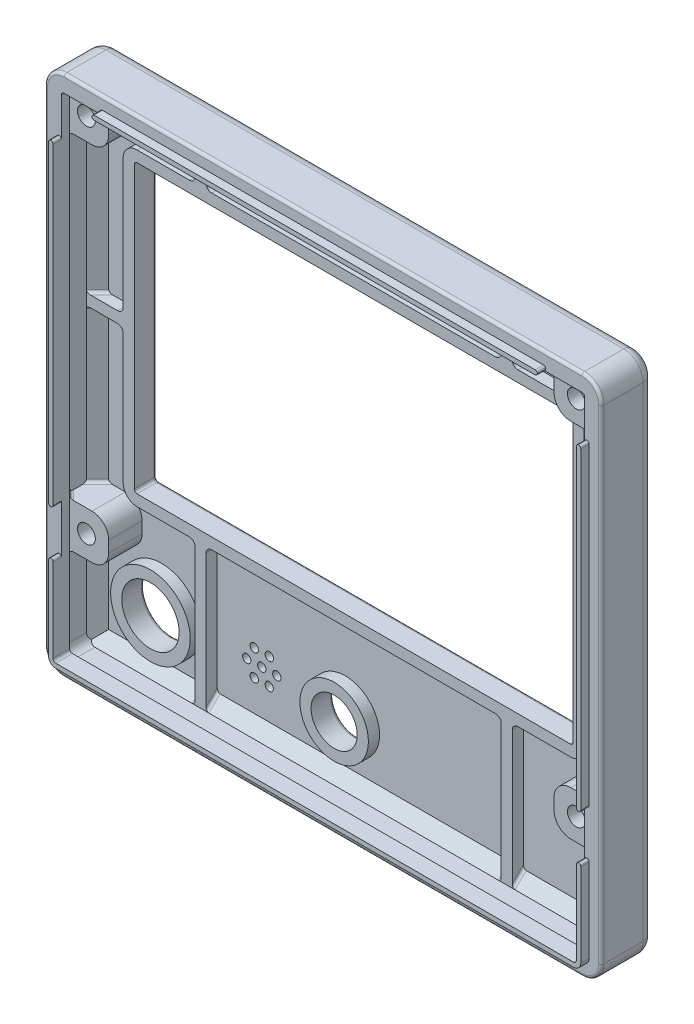
SolidWorks part; units mm, degrees
ref_plane "Спереди" through (0, 0, 0) normal (0, 0, 1) x (1, 0, 0)
ref_plane "Сверху" through (0, 0, 0) normal (0, 1, 0) x (1, 0, 0)
ref_plane "Справа" through (0, 0, 0) normal (1, 0, 0) x (0, 0, -1)
sketch "Эскиз1" plane through (0, 0, 0) normal (0, 0, 1) x (1, 0, 0)
  line L1 (-50, 46.95) -> (50, 46.95)
  line L2 (-50, 46.95) -> (-50, -46.95)
  line L3 (-50, -46.95) -> (50, -46.95)
  line L4 (50, 46.95) -> (50, -46.95)
  line L5 (-50, 46.95) -> (50, -46.95) construction
  line L6 (-50, -46.95) -> (50, 46.95) construction
  point P0 (0, 0)
  dimension "D1" = 100
  dimension "D2" = 93.9
extrude "Бобышка-Вытянуть1" add sketch "Эскиз1" along normal blind 2
sketch "Эскиз2" plane through (0, 0, 2) normal (0, 0, 1) x (1, 0, 0)
  line L0 (-48, -44.95) -> (48, -44.95)
  line L1 (50, -46.95) -> (-50, -46.95)
  line L2 (50, -46.95) -> (50, 46.95)
  line L3 (50, 46.95) -> (-50, 46.95)
  line L4 (-50, -46.95) -> (-50, 46.95)
  line L5 (50, -46.95) -> (-50, 46.95) construction
  line L6 (50, 46.95) -> (-50, -46.95) construction
  line L7 (48, -44.95) -> (48, -28.05)
  line L8 (48, -28.05) -> (40, -28.05)
  line L9 (40, -28.05) -> (40, -20.05)
  line L10 (40, -20.05) -> (48, -20.05)
  line L11 (48, -20.05) -> (48, 36.95)
  line L12 (48, 36.95) -> (40, 36.95)
  line L13 (40, 36.95) -> (40, 44.95)
  line L14 (40, 44.95) -> (-40, 44.95)
  line L15 (-40, 44.95) -> (-40, 36.95)
  line L16 (-40, 36.95) -> (-48, 36.95)
  line L17 (-48, 36.95) -> (-48, -20.05)
  line L18 (-48, -20.05) -> (-40, -20.05)
  line L19 (-40, -20.05) -> (-40, -28.05)
  line L20 (-40, -28.05) -> (-48, -28.05)
  line L21 (-48, -28.05) -> (-48, -44.95)
  line L22 (0, -3.7934) -> (0, 11.2679) construction
  line L23 (-44, 40.95) -> (44, 40.95) construction
  line L24 (-50, 46.95) -> (-28.7577, 25.7077) construction
  line L25 (44, -24.05) -> (-44, -24.05) construction
  line L26 (-44, -24.05) -> (-31.995, -12.045) construction
  line L27 (-41.4, 36.2) -> (41.4, 36.2)
  line L28 (-39.4, 34.2) -> (39.4, 34.2)
  line L29 (-39.4, 34.2) -> (-39.4, -17.3)
  line L30 (-39.4, -17.3) -> (39.4, -17.3)
  line L31 (39.4, 34.2) -> (39.4, -17.3)
  line L32 (-39.4, 34.2) -> (39.4, -17.3) construction
  line L33 (-39.4, -17.3) -> (39.4, 34.2) construction
  line L34 (41.4, 36.2) -> (41.4, -19.3)
  line L35 (-41.4, -19.3) -> (41.4, -19.3)
  line L36 (-41.4, 36.2) -> (-41.4, -19.3)
  line L37 (-45.7536, -35.05) -> (46.2117, -35.05) construction
  circle A0 centre (-44, 40.95) radius 1.6
  circle A1 centre (44, 40.95) radius 1.6
  circle A2 centre (-44, -24.05) radius 1.6
  circle A3 centre (44, -24.05) radius 1.6
  circle A4 centre (-36.5, -35.05) radius 5.15
  circle A5 centre (-18.5, -35.05) radius 0.75
  circle A6 centre (-21.2, -35.05) radius 0.75
  circle A7 centre (-3.5, -35.05) radius 4.15
  circle A8 centre (-19.85, -32.7117) radius 0.75
  circle A9 centre (-17.15, -32.7117) radius 0.75
  circle A10 centre (-15.8, -35.05) radius 0.75
  circle A11 centre (-17.15, -37.3883) radius 0.75
  circle A12 centre (-19.85, -37.3883) radius 0.75
  circle A13 centre (-3.5, -35.05) radius 6.15
  circle A14 centre (-36.5, -35.05) radius 7.15
  point P0 (0, 0)
  point P7 (0, 0)
  point P19 (0, 44.95)
  point P30 (0, 40.95)
  point P37 (40, -24.05)
  point P39 (0, 8.45)
  point P40 (0, -24.05)
  point P71 (-18.5, -35.05)
  line M5 (50, -46.95) -> (50, 46.95)
  line M6 (50, 46.95) -> (-50, 46.95)
  line M7 (-50, 46.95) -> (-50, -46.95)
  line M8 (-50, -46.95) -> (50, -46.95)
  dimension "D6" = 3.2
  dimension "D18" = 10.3
  dimension "D19" = 1.5
  dimension "D22" = 8.3
  dimension "D1" = 2
  dimension "D2" = 2
  dimension "D3" = 2
  dimension "D4" = 88
  dimension "D5" = 45
  dimension "D7" = 65
  dimension "D8" = 45
  dimension "D9" = 10
  dimension "D10" = 51.5
  dimension "D11" = 78.8
  dimension "D12" = 32.5
  dimension "D14" = 11
  dimension "D15" = 15
  dimension "D16" = 18
  dimension "D17" = 7.5
  dimension "D20" = 2.7
  dimension "D13" = 2
  dimension "D23" = 2
  dimension "D21" = 6
extrude "Бобышка-Вытянуть2" add sketch "Эскиз2" along normal blind 6 contours A3 A2 A1 A0 L21 L20 L19 L18 L17 L16 L15 L14 L13 L12 L11 L10 L9 L8 L7 L0 M8 M5 M6 M7 region at (0, -45.5782, 2)
ref_plane "Плоскость1" through (44, 0, 0) normal (1, 0, 0) x (0, 0, -1)
sketch "Эскиз6" plane through (44, 0, 0) normal (1, 0, 0) x (0, 0, -1)
  line L0 (-8, 42.55) -> (-8, 39.35) construction
  line L1 (-11.8886, 40.95) -> (4.8628, 40.95) construction
  line L2 (-8, 40.95) -> (-8, 42.55)
  line L3 (-8, -46.95) -> (-8, 46.95) construction
  line L4 (-8, 42.55) -> (-1.65, 42.55)
  line L5 (-1.65, 42.55) -> (-0.45, 43.75)
  line L6 (-0.45, 43.75) -> (0, 43.75)
  line L7 (0, -46.95) -> (0, 46.95) construction
  line L8 (0, 43.75) -> (0, 40.95)
  line L9 (0, 40.95) -> (-8, 40.95)
  point P2 (-8, 40.95)
  dimension "D1" = 5.6
  dimension "D2" = 1.65
  dimension "D3" = 45
  dimension "D4" = 3.2
revolve "Вырез-Повернуть1" cut sketch "Эскиз6" angle 360 about L1
pattern_linear "Линейный массив1" count 2 spacing 65 along (0, -1, 0) of "Вырез-Повернуть1"
mirror "Зеркальное отражение1" about plane through (0, 0, 0) normal (1, 0, 0) of "Линейный массив1", "Вырез-Повернуть1"
sketch "Эскиз3" plane through (0, 0, 8) normal (0, 0, 1) x (1, 0, 0)
  line L0 (40, 44.95) -> (-40, 44.95) construction
  line L1 (50, -46.95) -> (-50, -46.95)
  line L2 (50, -46.95) -> (50, 46.95)
  line L3 (50, 46.95) -> (-50, 46.95)
  line L4 (-50, -46.95) -> (-50, 46.95)
  line L5 (50, -46.95) -> (-50, 46.95) construction
  line L6 (50, 46.95) -> (-50, -46.95) construction
  line L7 (47, -43.95) -> (-47, -43.95)
  line L8 (47, -43.95) -> (47, 43.95)
  line L9 (47, 43.95) -> (-47, 43.95)
  line L10 (-47, -43.95) -> (-47, 43.95)
  line L11 (47, -43.95) -> (-47, 43.95) construction
  line L12 (47, 43.95) -> (-47, -43.95) construction
  line L13 (-48, -28.05) -> (-48, -44.95) construction
  point P0 (0, 0)
  point P7 (0, 0)
  dimension "D1" = 1
  dimension "D2" = 1
extrude "Бобышка-Вытянуть3" add sketch "Эскиз3" along normal blind 1.5
sketch "Эскиз4" plane through (0, 0, 9.5) normal (0, 0, 1) x (1, 0, 0)
  line L0 (-47, -43.95) -> (-47, -28.05)
  line L1 (-47, -28.05) -> (-47.8, -28.05)
  line L2 (-47.8, -28.05) -> (-47.8, -44.75)
  line L3 (-47.8, -44.75) -> (47.8, -44.75)
  line L4 (47.8, -44.75) -> (47.8, -28.05)
  line L5 (47.8, -28.05) -> (47, -28.05)
  line L6 (47, -28.05) -> (47, -43.95)
  line L7 (47, -43.95) -> (-47, -43.95)
  line L8 (-47, -20.05) -> (-47, 36.95)
  line L9 (-40, 36.95) -> (-48, 36.95) construction
  line L11 (-47, 36.95) -> (-47.8, 36.95)
  line L12 (-47.8, 36.95) -> (-47.8, -20.05)
  line L13 (-47.8, -20.05) -> (-47, -20.05)
  line L14 (47, -20.05) -> (47, 36.95)
  line L15 (47, 36.95) -> (47.8, 36.95)
  line L16 (47.8, 36.95) -> (47.8, -20.05)
  line L17 (47.8, -20.05) -> (47, -20.05)
  line L18 (-40, 43.95) -> (-40, 44.75)
  line L19 (-40, 44.75) -> (40, 44.75)
  line L20 (40, 44.75) -> (40, 43.95)
  line L21 (40, 43.95) -> (-40, 43.95)
  dimension "D1" = 0.8
  dimension "D2" = 0.8
extrude "Бобышка-Вытянуть4" add sketch "Эскиз4" along normal blind 1.5
extrude "Вырез-Вытянуть1" cut sketch "Эскиз2<3>" against normal through all contours L31 L28 L29 L30 | A4 | A6 | A5 | A8 | A9 | A10 | A11 | A12 | A7 region at (0, 8.45, 2) region at (-36.5, -35.05, 2) region at (-18.5, -35.05, 2) region at (-21.2, -35.05, 2) region at (-3.5, -35.05, 2) region at (-19.85, -32.7117, 2) region at (-17.15, -32.7117, 2) region at (-15.8, -35.05, 2) region at (-17.15, -37.3883, 2) region at (-19.85, -37.3883, 2)
sketch "Эскиз2<3>" plane through (0, 0, 2) normal (0, 0, 1) x (1, 0, 0) same geometry as "Эскиз2"
extrude "Бобышка-Вытянуть5" add sketch "Эскиз2<4>" along normal blind 2 contours A14 A4 | A13 A7 | L27 L36 L35 L34 L28 L31 L30 L29 region at (0, 35.2032, 2) region at (-9.4761, -35.05, 2) region at (-43.4478, -35.05, 2)
sketch "Эскиз2<4>" plane through (0, 0, 2) normal (0, 0, 1) x (1, 0, 0) same geometry as "Эскиз2"
fillet "Скругление1" radius 3 6 edges at (40, -20.05, 5) (40, -28.05, 5) (40, 36.95, 5) (-40, -20.05, 5) (-40, -28.05, 5) (-40, 36.95, 5)
fillet "Скругление2" radius 0.5 4 edges at (47, -43.95, 9.5) (47, 43.95, 8.75) (-47, 43.95, 8.75) (-47, -43.95, 9.5)
fillet "Скругление3" radius 1.3 2 edges at (47.8, -44.75, 10.25) (-47.8, -44.75, 10.25)
fillet "Скругление4" radius 3.5 4 edges at (50, 46.95, 4.75) (-50, 46.95, 4.75) (-50, -46.95, 4.75) (50, -46.95, 4.75)
fillet "Скругление5" radius 0.4 16 edges at (-47, 36.95, 10.25) (-47.8, 36.95, 10.25) (-40, 44.75, 10.25) (-40, 43.95, 10.25) (40, 44.75, 10.25) (40, 43.95, 10.25) (47.8, 36.95, 10.25) (47, 36.95, 10.25) (47.8, -20.05, 10.25) (47, -20.05, 10.25) (47.8, -28.05, 10.25) (-47.8, -28.05, 10.25) (-47, -20.05, 10.25) (-47.8, -20.05, 10.25)
fillet "Скругление11" radius 2 8 edges at (-48.9749, -45.9249, 0) (-50, 0, 0) (-48.9749, 45.9249, 0) (0, 46.95, 0) (48.9749, 45.9249, 0) (50, 0, 0) (48.9749, -45.9249, 0) (0, -46.95, 0)
fillet "Скругление12" radius 0.5 8 edges at (-48.9749, 45.9249, 9.5) (0, 46.95, 9.5) (48.9749, 45.9249, 9.5) (50, 0, 9.5) (48.9749, -45.9249, 9.5) (0, -46.95, 9.5) (-48.9749, -45.9249, 9.5) (-50, 0, 9.5)
fillet "Скругление14" radius 0.5 10 edges at (0, 34.2, 0) (-39.4, 8.45, 0) (39.4, 8.45, 0) (0, -17.3, 0) (39.4, -17.3, 2) (39.4, 34.2, 2) (-39.4, 34.2, 2) (-39.4, -17.3, 2) (-31.35, -35.05, 0) (0.65, -35.05, 0)
fillet "Скругление15" radius 2.5 4 edges at (-41.4, -19.3, 3) (-41.4, 36.2, 3) (41.4, 36.2, 3) (41.4, -19.3, 3)
sketch "Эскиз5" plane through (0, 0, 2) normal (0, 0, 1) x (1, 0, 0)
  line L0 (-18.5, -35.05) -> (-36.5, -35.05) construction
  line L1 (0, 17.7413) -> (0, -7.0875) construction
  line L2 (-27.5, -51.2657) -> (-27.5, 49.7619) construction
  line L3 (27.5, -48.9866) -> (-27.5, -48.9866) construction
  line L4 (27.5, -51.2657) -> (27.5, 49.7619) construction
  line L5 (-39.4, 33.7) -> (-39.4, -16.8) construction
  line L6 (-62.052, 8.45) -> (56.1888, 8.45) construction
  line L7 (-38.9, -19.3) -> (38.9, -19.3) construction
  line L8 (-28.5, 44.95) -> (-26.5, 44.95)
  line L9 (-28.5, 44.95) -> (-28.5, 36.2)
  line L10 (-28.5, 36.2) -> (-26.5, 36.2)
  line L11 (-26.5, 44.95) -> (-26.5, 36.2)
  line L12 (26.5, 44.95) -> (28.5, 44.95)
  line L13 (26.5, 44.95) -> (26.5, 36.2)
  line L14 (26.5, 36.2) -> (28.5, 36.2)
  line L15 (28.5, 44.95) -> (28.5, 36.2)
  line L16 (41.4, 9.45) -> (48, 9.45)
  line L17 (41.4, 9.45) -> (41.4, 7.45)
  line L18 (41.4, 7.45) -> (48, 7.45)
  line L19 (48, 9.45) -> (48, 7.45)
  line L20 (-48, 9.45) -> (-41.4, 9.45)
  line L21 (-48, 9.45) -> (-48, 7.45)
  line L22 (-48, 7.45) -> (-41.4, 7.45)
  line L23 (-41.4, 9.45) -> (-41.4, 7.45)
  line L24 (-28.5, -19.3) -> (-26.5, -19.3)
  line L25 (-28.5, -19.3) -> (-28.5, -44.95)
  line L26 (-28.5, -44.95) -> (-26.5, -44.95)
  line L27 (-26.5, -19.3) -> (-26.5, -44.95)
  line L28 (26.5, -19.3) -> (28.5, -19.3)
  line L29 (26.5, -19.3) -> (26.5, -44.95)
  line L30 (26.5, -44.95) -> (28.5, -44.95)
  line L31 (28.5, -19.3) -> (28.5, -44.95)
  line L32 (-48, -44.95) -> (48, -44.95) construction
  line L34 (48, -20.05) -> (48, 36.95) construction
  line L35 (41.4, 33.7) -> (41.4, -16.8) construction
  line L36 (-41.4, 33.7) -> (-41.4, -16.8) construction
  line L37 (-48, 36.95) -> (-48, -20.05) construction
  line L38 (-38.9, 36.2) -> (38.9, 36.2) construction
  line L39 (40, 44.95) -> (-40, 44.95) construction
  line L40 (40, 44.95) -> (-40, 44.95) construction
  line L41 (-38.9, 36.2) -> (38.9, 36.2) construction
  point P0 (-36.5, -35.05)
  point P3 (-27.5, -35.05)
  point P4 (-18.5, -35.05)
  point P15 (0, -48.9866)
  point P17 (-39.4, 8.45)
  point P46 (-27.5, -19.3)
  point P47 (-41.4, 8.45)
  point P48 (-27.5, 44.95)
  point P49 (27.5, 44.95)
  point P50 (48, 8.45)
  point P51 (27.5, -19.3)
  dimension "D1" = 2
extrude "Бобышка-Вытянуть6" add sketch "Эскиз5" along normal blind 2
chamfer "Фаска3" distance 2 angle 45 12 edges at (34.25, 44.95, 2) (-34.25, 44.95, 2) (48, -6.3, 2) (48, 23.2, 2) (-48, -6.3, 2) (-48, 23.2, 2) (48, -36.5, 2) (-48, -36.5, 2) (-38.25, -44.95, 2) (38.25, -44.95, 2) (0, 44.95, 2) (0, -44.95, 2)
chamfer "Фаска4" distance 1 angle 45 6 edges at (0, 44.95, 8) (-48, 8.45, 8) (48, 8.45, 8) (-48, -36.5, 8) (48, -36.5, 8) (0, -44.95, 8)
fillet "Скругление13" radius 1.5 2 edges at (-48, -44.95, 5.5) (48, -44.95, 5.5)
fillet "Скругление17" radius 1 12 edges at (41.4, 9.45, 3) (41.4, 7.45, 3) (28.5, -19.3, 3) (26.5, -19.3, 3) (-26.5, -19.3, 3) (-28.5, -19.3, 3) (-41.4, 9.45, 3) (-41.4, 7.45, 3) (-26.5, 36.2, 3) (-28.5, 36.2, 3) (28.5, 36.2, 3) (26.5, 36.2, 3)
fillet "Скругление18" radius 0.5 28 edges at (-47.5, 36.95, 7.5) (-47, 36.95, 3) (-47.5, -20.05, 7.5) (-47, -20.05, 3) (-47.5, -28.05, 7.5) (-47, -28.05, 3) (47.5, -28.05, 7.5) (47, -28.05, 3) (47.5, -20.05, 7.5) (47, -20.05, 3) (47.5, 36.95, 7.5) (47, 36.95, 3) (40, 44.45, 7.5) (40, 43.95, 3) (-47, 9.45, 3) (-47, 7.45, 3) (-28.5, -43.95, 3) (-26.5, -43.95, 3) (26.5, -43.95, 3) (28.5, -43.95, 3) (47, 7.45, 3) (47, 9.45, 3) (28.5, 43.95, 3) (26.5, 43.95, 3) (-28.5, 43.95, 3) (-26.5, 43.95, 3) (-40, 44.45, 7.5) (-40, 43.95, 3)
equation "\"D2@Эскиз1\"=86.9+(0.5+1+2)*2"
equation "\"D1@Эскиз1\"=93+(0.5+1+2)*2"
